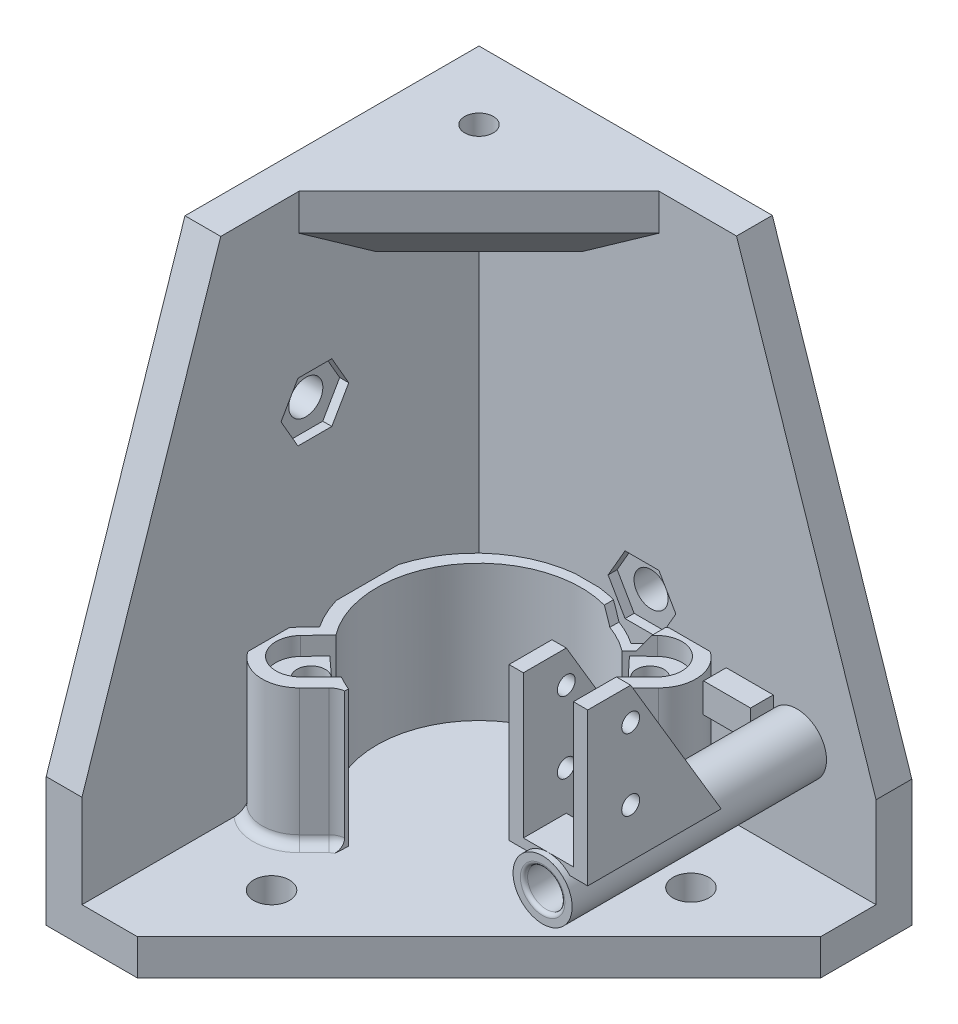
SolidWorks part; units mm, degrees
ref_plane "Front" through (0, 0, 0) normal (0, 0, 1) x (1, 0, 0)
ref_plane "Top" through (0, 0, 0) normal (0, 1, 0) x (1, 0, 0)
ref_plane "Right" through (0, 0, 0) normal (1, 0, 0) x (0, 0, -1)
sketch "Sketch1" plane through (0, 0, 0) normal (0, 1, 0) x (1, 0, 0)
  line L0 (0, 0) -> (0, 60.5)
  line L1 (0, -55) -> (0, 55) construction
  line L2 (0, 60.5) -> (60.5, 60.5)
  line L3 (60.5, 60.5) -> (60.5, 47.75)
  line L4 (60.5, 47.75) -> (12.75, 0)
  line L5 (-55, 0) -> (55, 0) construction
  line L6 (12.75, 0) -> (0, 0)
  dimension "D1" = 60.5
  dimension "D2" = 12.75
extrude "Boss-Extrude1" add sketch "Sketch1" along normal blind 5
sketch "Sketch4" plane through (0, 0, 0) normal (-1, 0, 0) x (0, 0, 1)
  line L0 (-60.5, 5) -> (-60.5, 76.1962)
  line L1 (-60.5, 76.1962) -> (-19.4, 76.1962)
  line L2 (-19.4, 76.1962) -> (0, 18.0048)
  line L3 (0, 18.0048) -> (0, 5)
  line L4 (0, -2.75) -> (0, 2.75) construction
  line L5 (-60.5, 5) -> (0, 5) construction
  line L6 (-60.5, 5) -> (0, 5)
  dimension "D1" = 71.1962
  dimension "D2" = 41.1
  dimension "D3" = 61.34
extrude "Boss-Extrude2" add sketch "Sketch4" against normal blind 5
sketch "Sketch5" plane through (0, 0, -60.5) normal (0, 0, -1) x (-1, 0, 0)
  line L0 (0, 76.1962) -> (-41, 76.1962)
  line L1 (-41, 76.1962) -> (-60.5, 17.7009)
  line L2 (-60.5, 17.7009) -> (-60.5, 5)
  line L6 (-60.5, 0) -> (0, 0)
  line L7 (0, 0) -> (0, 76.1962)
  line L8 (0, 76.1962) -> (-5, 76.1962)
  line L9 (-5, 76.1962) -> (-5, 5)
  line L10 (-5, 5) -> (-60.5, 5)
  line L11 (-60.5, 5) -> (-60.5, 0)
  line L12 (-60.5, 0) -> (0, 0)
  line L13 (0, 0) -> (0, 76.1962)
  line L14 (0, 76.1962) -> (-5, 76.1962)
  line L15 (-5, 76.1962) -> (-5, 5)
  line L16 (-5, 5) -> (-60.5, 5)
  line L17 (-60.5, 5) -> (-60.5, 0)
  line M13 (-5, 76.1962) -> (-5, 5)
  line M14 (-5, 5) -> (-60.5, 5)
  dimension "D2" = 41
  dimension "D3" = 61.66
  dimension "D1" = 0
extrude "Boss-Extrude3" add sketch "Sketch5" against normal blind 5 contours L1 L2 L0 M14 M13 region at (29.1655, 37.8824, -60.5)
sketch "Sketch6" plane through (0, 5, 0) normal (0, 1, 0) x (1, 0, 0)
  line L0 (60.5, 60.5) -> (0, 60.5) construction
  line L4 (0, 19.4) -> (0, 0)
  line L5 (60.5, 55.5) -> (5, 55.5)
  line L6 (5, 55.5) -> (5, 0)
  line L7 (5, 0) -> (12.75, 0)
  line L8 (12.75, 0) -> (60.5, 47.75)
  line L9 (60.5, 47.75) -> (60.5, 55.5)
  line L10 (60.5, 55.5) -> (5, 55.5)
  line L11 (5, 55.5) -> (5, 0)
  line L12 (5, 0) -> (12.75, 0)
  line L13 (12.75, 0) -> (60.5, 47.75)
  line L14 (60.5, 47.75) -> (60.5, 55.5)
  line L15 (0, 0) -> (5, 0)
  line L16 (5, 0) -> (5, 19.4)
  line L17 (5, 19.4) -> (0, 19.4)
  line L18 (0, 19.4) -> (0, 0)
  line L19 (0, 0) -> (5, 0)
  line L20 (5, 0) -> (5, 19.4)
  line L21 (5, 19.4) -> (0, 19.4)
  line L24 (0, 60.5) -> (0, 19.4)
  line L25 (0, 19.4) -> (5, 19.4)
  line L26 (5, 19.4) -> (5, 55.5)
  line L27 (5, 55.5) -> (41, 55.5)
  line L28 (41, 55.5) -> (41, 60.5)
  line L29 (41, 60.5) -> (0, 60.5)
  line L30 (0, 60.5) -> (0, 19.4)
  line L31 (0, 19.4) -> (5, 19.4)
  line L32 (5, 19.4) -> (5, 55.5)
  line L33 (5, 55.5) -> (41, 55.5)
  line L34 (41, 55.5) -> (41, 60.5)
  line L35 (41, 60.5) -> (0, 60.5)
  circle A0 centre (16.5, 15) radius 2.5
  circle A1 centre (45.5, 44.625) radius 2.5
  dimension "D1" = 5
  dimension "D2" = 5
  dimension "D3" = 0
  dimension "D4" = 15
  dimension "D6" = 16.5
  dimension "D7" = 15
  dimension "D9" = 15.875
  dimension "D5" = 0
  dimension "D8" = 0
extrude "Cut-Extrude1" cut sketch "Sketch6" against normal through all contours A0 | A1 region at (16.5, 5, -15) region at (45.5, 5, -44.625)
sketch "Sketch9" plane through (0, 0, -55.5) normal (0, 0, 1) x (1, 0, 0)
  line L1 (5, 76.1962) -> (5, 5) construction
  line L5 (0, 0) -> (60.5, 0)
  line L6 (0, 76.1962) -> (0, 0)
  line L7 (41, 76.1962) -> (0, 76.1962)
  line L8 (60.5, 17.7009) -> (41, 76.1962)
  line L9 (60.5, 0) -> (60.5, 17.7009)
  line L10 (0, 0) -> (60.5, 0)
  line L11 (0, 76.1962) -> (0, 0)
  line L12 (41, 76.1962) -> (0, 76.1962)
  line L13 (60.5, 17.7009) -> (41, 76.1962)
  line L14 (60.5, 0) -> (60.5, 17.7009)
  line L15 (49.45, 19.0462) -> (49.45, 3.6199) construction
  circle A0 centre (49.45, 19.0462) radius 4.1275
  circle A1 centre (49.45, 19.0462) radius 2.6035
  dimension "D2" = 5.207
  dimension "D3" = 1.524
  dimension "D4" = 57.15
  dimension "D5" = 44.45
  dimension "D1" = 0
extrude "Boss-Extrude5" add sketch "Sketch9" along normal blind 35.56 contours A1 A0 region at (45.4392, 19.0462, -55.5)
fillet "Fillet1" radius 0.508 1 edges at (52.0535, 19.0462, -19.94)
sketch "Sketch14" plane through (0, 5, 0) normal (0, 1, 0) x (1, 0, 0)
  line L0 (13.4627, 27.5396) -> (14.7681, 26.7924)
  line L1 (12.75, 0) -> (60.5, 47.75) construction
  line L2 (36.625, 23.875) -> (5, 55.5) construction
  line L3 (5, 55.5) -> (60.5, 55.5) construction
  line L4 (32.9604, 47.0373) -> (33.7076, 45.7319)
  line L5 (14.8281, 26.8523) -> (11.8274, 23.8516)
  line L6 (6.723, 28.8027) -> (9.1327, 31.3641)
  line L7 (33.6477, 45.6719) -> (36.6484, 48.6726)
  line L8 (31.6973, 53.777) -> (29.1359, 51.3673)
  line L9 (15.0744, 24.4582) -> (13.006, 22.3898)
  line L10 (5.6561, 29.7396) -> (7.0609, 31.1444)
  line L11 (36.0418, 45.4256) -> (38.1102, 47.494)
  line L12 (30.7604, 54.8439) -> (28.83, 52.9135)
  line L13 (18.1324, 24.8665) -> (30.5234, 17.7734)
  line L14 (35.6335, 42.3676) -> (42.7266, 29.9766)
  line L15 (31.7409, 18.9909) -> (18.852, 25.7543)
  line L16 (41.5091, 28.7591) -> (34.7457, 41.648)
  line L17 (16.5689, 25.6946) -> (16.5343, 25.1798)
  line L18 (34.7457, 41.648) -> (35.7996, 42.0774)
  circle A0 centre (20.5607, 39.9393) radius 14.2875
  arc A1 (11.8274, 23.8516) -> (6.723, 28.8027) centre (9.3129, 26.3661) cw
  arc A2 (36.6484, 48.6726) -> (31.6973, 53.777) centre (34.1339, 51.1871) ccw
  arc A3 (13.006, 22.3898) -> (5.6561, 29.7396) centre (9.3311, 26.0647) cw
  arc A4 (38.1102, 47.494) -> (30.7604, 54.8439) centre (34.4353, 51.1689) ccw
  arc A5 (7.0609, 31.1444) -> (28.83, 52.9135) centre (20.0709, 39.9035) cw
  arc A6 (36.0418, 45.4256) -> (35.6335, 42.3676) centre (37.8378, 43.6295) ccw
  arc A7 (15.0744, 24.4582) -> (18.1324, 24.8665) centre (16.8705, 22.6622) cw
  arc A9 (33.8602, 45.8844) -> (36.3595, 38.5726) centre (13.6025, 34.877) cw
  arc A10 (14.6156, 26.6398) -> (21.9274, 24.1405) centre (25.623, 46.8975) ccw
  point P40 (34.6689, 44.0527)
  point P43 (16.4473, 25.8311)
  line M13 (60.5, 55.5) -> (5, 55.5)
  line M14 (5, 55.5) -> (5, 0)
  line M16 (12.75, 0) -> (60.5, 47.75)
  dimension "D1" = 28.575
  dimension "D2" = 3.556
  dimension "D3" = 2.54
extrude "Boss-Extrude6" add sketch "Sketch14" along normal blind 19.05 contours L2 A0 L5 A1 L6 A5 L10 A3 L9 A7 L13 M16 M14 | L2 L14 A6 L11 A4 L12 A5 A0 L8 A2 L7 M16 M13 region at (7.691, 5, -30.3062) region at (10.0875, 5, -50.8829)
sketch "Sketch15" plane through (0, 76.1962, 0) normal (0, 1, 0) x (1, 0, 0)
  line L0 (5, 30.3375) -> (30.1625, 55.5)
  line L1 (0, -33.275) -> (0, 33.275) construction
  line L2 (41, 60.5) -> (0, 60.5) construction
  line L6 (0, 60.5) -> (0, 19.4)
  line L7 (0, 19.4) -> (5, 19.4)
  line L8 (5, 19.4) -> (5, 55.5)
  line L9 (5, 55.5) -> (41, 55.5)
  line L10 (41, 55.5) -> (41, 60.5)
  line L11 (41, 60.5) -> (0, 60.5)
  line L13 (0, 19.4) -> (5, 19.4)
  line L14 (5, 30.3375) -> (5, 55.5)
  line L15 (5, 55.5) -> (30.1625, 55.5)
  line L16 (41, 55.5) -> (41, 60.5)
  circle A0 centre (9.525, 50.975) radius 2
  line M11 (5, 19.4) -> (5, 55.5)
  line M12 (5, 55.5) -> (41, 55.5)
  dimension "D3" = 4
  dimension "D4" = 9.525
  dimension "D5" = 9.525
  dimension "D2" = 45
  dimension "D1" = 0
extrude "Boss-Extrude7" add sketch "Sketch15" against normal blind 12.7 contours L0 A0 M11 M12 region at (13.5472, 76.1962, -46.9528)
chamfer "Chamfer2" distance 7.62 angle 45 1 edges at (17.5813, 63.4962, -42.9187)
fillet "Fillet2" radius 1.27 7 edges at (39.6065, 5, -51.6871) (37.076, 5, -46.4598) (35.3202, 5, -43.9657) (8.8129, 5, -20.8935) (14.0402, 5, -23.424) (15.745, 5, -24.9392) (35.7165, 5, -42.2225)
sketch "Sketch16" plane through (0, 0, -55.5) normal (0, 0, 1) x (1, 0, 0)
  line L1 (46.1305, 23.2107) -> (38.2864, 23.2107)
  line L2 (46.1305, 23.2107) -> (46.1305, 19.0978)
  line L3 (46.1305, 19.0978) -> (38.2864, 19.0978)
  line L4 (38.2864, 23.2107) -> (38.2864, 19.0978)
extrude "Boss-Extrude8" add sketch "Sketch16" along normal blind 3.175
chamfer "Chamfer3" distance 1.27 angle 45 1 edges at (38.2864, 23.2107, -55.0794)
sketch "Sketch17" plane through (0, 5, 0) normal (0, 1, 0) x (1, 0, 0)
  line L0 (8.716, 30.9212) -> (14.047, 26.0712)
  line L1 (36.625, 23.875) -> (5, 55.5) construction
  line L2 (12.75, 0) -> (60.5, 47.75) construction
  line L3 (5, 55.5) -> (18.418, 55.5) construction
  line L4 (5, 55.5) -> (5, 44.2452) construction
  line L5 (29.6632, 51.8634) -> (34.5959, 46.6202)
  line L22 (37.3079, 55.5) -> (31.5627, 55.5)
  line L23 (30.7604, 54.8439) -> (28.83, 52.9135)
  line L24 (21.7238, 55.5) -> (18.418, 55.5)
  line L25 (5, 44.2452) -> (5, 35.5618)
  line L26 (7.0609, 31.1444) -> (5.6561, 29.7396)
  line L27 (5, 28.9373) -> (5, 23.1921)
  line L28 (13.006, 22.3898) -> (15.0744, 24.4582)
  line L29 (16.5343, 25.1798) -> (16.5689, 25.6946)
  line L30 (16.5343, 25.1798) -> (16.5689, 25.6946)
  line L31 (35.539, 41.9712) -> (35.7996, 42.0774)
  line L32 (35.539, 41.9712) -> (35.7996, 42.0774)
  line L33 (14.6156, 26.6398) -> (11.8274, 23.8516)
  line L34 (6.723, 28.8027) -> (9.1327, 31.3641)
  line L35 (29.1359, 51.3673) -> (31.6973, 53.777)
  line L36 (36.6484, 48.6726) -> (33.8602, 45.8844)
  line L40 (35.7996, 42.0774) -> (35.6335, 42.3676)
  line L41 (36.0418, 45.4256) -> (38.1102, 47.494)
  line L43 (37.3079, 55.5) -> (31.5627, 55.5)
  line L44 (30.7604, 54.8439) -> (28.83, 52.9135)
  line L45 (21.7238, 55.5) -> (18.418, 55.5)
  line L46 (5, 44.2452) -> (5, 35.5618)
  line L47 (7.0609, 31.1444) -> (5.6561, 29.7396)
  line L48 (5, 28.9373) -> (5, 23.1921)
  line L49 (13.006, 22.3898) -> (15.0744, 24.4582)
  line L54 (14.6156, 26.6398) -> (11.8274, 23.8516)
  line L55 (6.723, 28.8027) -> (9.1327, 31.3641)
  line L56 (29.1359, 51.3673) -> (31.6973, 53.777)
  line L57 (36.6484, 48.6726) -> (33.8602, 45.8844)
  line L61 (35.7996, 42.0774) -> (35.6335, 42.3676)
  line L62 (36.0418, 45.4256) -> (38.1102, 47.494)
  circle A1 centre (33.6908, 50.7324) radius 2.1828
  circle A2 centre (10.0204, 27.0078) radius 1.9844
  circle A3 centre (33.6908, 50.7324) radius 1.9288
  arc A15 (38.1102, 47.494) -> (37.3079, 55.5) centre (34.4353, 51.1689) ccw
  arc A17 (31.5627, 55.5) -> (30.7604, 54.8439) centre (34.4353, 51.1689) ccw
  arc A18 (28.83, 52.9135) -> (21.7238, 55.5) centre (20.0709, 39.9035) ccw
  arc A19 (18.418, 55.5) -> (5, 44.2452) centre (20.0709, 39.9035) ccw
  arc A20 (5, 35.5618) -> (7.0609, 31.1444) centre (20.0709, 39.9035) ccw
  arc A21 (5.6561, 29.7396) -> (5, 28.9373) centre (9.3311, 26.0647) ccw
  arc A22 (5, 23.1921) -> (13.006, 22.3898) centre (9.3311, 26.0647) ccw
  arc A23 (16.5343, 25.1798) -> (15.0744, 24.4582) centre (16.8705, 22.6622) ccw
  arc A24 (14.6156, 26.6398) -> (16.5689, 25.6946) centre (25.623, 46.8975) ccw
  arc A25 (6.723, 28.8027) -> (11.8274, 23.8516) centre (9.3129, 26.3661) ccw
  arc A26 (29.1359, 51.3673) -> (9.1327, 31.3641) centre (20.5607, 39.9393) ccw
  arc A27 (36.6484, 48.6726) -> (31.6973, 53.777) centre (34.1339, 51.1871) ccw
  arc A28 (35.539, 41.9712) -> (33.8602, 45.8844) centre (13.6025, 34.877) ccw
  arc A29 (36.0418, 45.4256) -> (35.6335, 42.3676) centre (37.8378, 43.6295) ccw
  arc A30 (38.1102, 47.494) -> (37.3079, 55.5) centre (34.4353, 51.1689) ccw
  arc A32 (31.5627, 55.5) -> (30.7604, 54.8439) centre (34.4353, 51.1689) ccw
  arc A33 (28.83, 52.9135) -> (21.7238, 55.5) centre (20.0709, 39.9035) ccw
  arc A34 (18.418, 55.5) -> (5, 44.2452) centre (20.0709, 39.9035) ccw
  arc A35 (5, 35.5618) -> (7.0609, 31.1444) centre (20.0709, 39.9035) ccw
  arc A36 (5.6561, 29.7396) -> (5, 28.9373) centre (9.3311, 26.0647) ccw
  arc A37 (5, 23.1921) -> (13.006, 22.3898) centre (9.3311, 26.0647) ccw
  arc A38 (16.5343, 25.1798) -> (15.0744, 24.4582) centre (16.8705, 22.6622) ccw
  arc A39 (14.6156, 26.6398) -> (16.5689, 25.6946) centre (25.623, 46.8975) ccw
  arc A40 (6.723, 28.8027) -> (11.8274, 23.8516) centre (9.3129, 26.3661) ccw
  arc A41 (29.1359, 51.3673) -> (9.1327, 31.3641) centre (20.5607, 39.9393) ccw
  arc A42 (36.6484, 48.6726) -> (31.6973, 53.777) centre (34.1339, 51.1871) ccw
  arc A43 (35.539, 41.9712) -> (33.8602, 45.8844) centre (13.6025, 34.877) ccw
  arc A44 (36.0418, 45.4256) -> (35.6335, 42.3676) centre (37.8378, 43.6295) ccw
  line M44 (33.8602, 45.8844) -> (36.6484, 48.6726)
  arc M45 (36.6484, 48.6726) -> (31.6973, 53.777) centre (34.1339, 51.1871) ccw
  line M46 (31.6973, 53.777) -> (29.1359, 51.3673)
  line M48 (9.1327, 31.3641) -> (6.723, 28.8027)
  arc M49 (6.723, 28.8027) -> (11.8274, 23.8516) centre (9.3129, 26.3661) ccw
  line M50 (11.8274, 23.8516) -> (14.6156, 26.6398)
  dimension "D2" = 3.9688
  dimension "D3" = 0.254
  dimension "D1" = 0
extrude "Boss-Extrude9" add sketch "Sketch17" along normal offset from surface (16.51 mm away) 2.54 contours L5 A1 M46 M44 M45 | L0 M48 M49 M50 | A1 L5 A3 region at (11.3737, 5, -28.4876) region at (30.7585, 5, -52.737) region at (33.0584, 5, -52.7569) up to face at (20.9693, 24.05, -39.9839)
sketch "Sketch18" plane through (0, 0, 0) normal (-1, 0, 0) x (0, 0, 1)
  line L0 (-60.5, 76.1962) -> (-60.5, 0) construction
  line L1 (33.275, 0) -> (-33.275, 0) construction
  circle A0 centre (-32.56, 49.53) radius 2.3813
  dimension "D1" = 27.94
  dimension "D2" = 49.53
  dimension "D3" = 4.7625
extrude "Cut-Extrude2" cut sketch "Sketch18" against normal up to next
sketch "Sketch19" plane through (0, 0, -60.5) normal (0, 0, -1) x (-1, 0, 0)
  line L0 (0, 33.275) -> (0, -33.275) construction
  line L1 (33.275, 0) -> (-33.275, 0) construction
  circle A0 centre (-27.7812, 26.1937) radius 2.3813
  dimension "D1" = 27.7812
  dimension "D2" = 26.1937
  dimension "D3" = 4.7625
extrude "Cut-Extrude3" cut sketch "Sketch19" against normal up to next
sketch "Sketch20" plane through (0, 0, -55.5) normal (0, 0, 1) x (1, 0, 0)
  line L1 (32.5155, 26.1938) -> (30.1484, 30.2938)
  line L2 (30.1484, 30.2938) -> (25.4141, 30.2938)
  line L3 (25.4141, 30.2938) -> (23.047, 26.1938)
  line L4 (23.047, 26.1938) -> (25.4141, 22.0938)
  line L5 (25.4141, 22.0938) -> (30.1484, 22.0938)
  line L6 (30.1484, 22.0938) -> (32.5155, 26.1938)
  circle A0 centre (27.7812, 26.1937) radius 2.3813 construction
  circle A1 centre (27.7812, 26.1937) radius 2.3813
  circle A2 centre (27.7812, 26.1937) radius 4.1 construction
  dimension "D1" = 8.2
extrude "Cut-Extrude4" cut sketch "Sketch20" against normal blind 1.27 and the other way up to vertex (4.1327 mm away) contours L1 L2 L3 L4 L5 L6 other way up to point (29.1359, 24.05, -51.3673)
sketch "Sketch21" plane through (5, 0, 0) normal (1, 0, 0) x (0, 0, -1)
  line L1 (34.9271, 53.63) -> (30.1929, 53.63)
  line L2 (30.1929, 53.63) -> (27.8257, 49.53)
  line L3 (27.8257, 49.53) -> (30.1929, 45.43)
  line L4 (30.1929, 45.43) -> (34.9271, 45.43)
  line L5 (34.9271, 45.43) -> (37.2943, 49.53)
  line L6 (37.2943, 49.53) -> (34.9271, 53.63)
  circle A0 centre (32.56, 49.53) radius 2.3813 construction
  circle A1 centre (32.56, 49.53) radius 2.3812
  circle A2 centre (32.56, 49.53) radius 4.1 construction
  dimension "D1" = 8.2
extrude "Cut-Extrude5" cut sketch "Sketch21" against normal blind 1.27 contours L1 L2 L3 L4 L5 L6
sketch "Sketch23" plane through (0, 0, 0) normal (0, 1, 0) x (1, 0, 0)
  line L1 (60.5, 60.5) -> (101.14, 60.5)
  line L2 (60.5, 60.5) -> (60.5, 24.94)
  line L3 (60.5, 24.94) -> (101.14, 24.94)
  line L4 (101.14, 60.5) -> (101.14, 24.94)
  dimension "D1" = 40.64
  dimension "D2" = 35.56
extrude "Boss-Extrude12" [suppressed] add sketch "Sketch23" along normal blind 5.08
sketch "Sketch24" [suppressed] plane through (0, 5.08, 0) normal (0, 1, 0) x (1, 0, 0)
  line L0 (101.14, 60.5) -> (60.5, 60.5) construction
  line L1 (60.5, 47.75) -> (60.5, 55.5) construction
  circle A0 centre (65.58, 55.42) radius 1.7145
  circle A1 centre (96.06, 55.42) radius 1.7145
  circle A2 centre (96.06, 29.258) radius 1.7145
  circle A3 centre (65.58, 29.258) radius 1.7145
  dimension "D1" = 3.429
  dimension "D2" = 26.162
  dimension "D3" = 30.48
  dimension "D4" = 5.08
  dimension "D5" = 5.08
extrude "Cut-Extrude6" [suppressed] cut sketch "Sketch24" against normal up to next
sketch "Sketch25" plane through (0, 63.4962, 0) normal (0, -1, 0) x (1, 0, 0)
  line L1 (13.5665, -50.975) -> (11.5457, -47.475)
  line L2 (11.5457, -47.475) -> (7.5043, -47.475)
  line L3 (7.5043, -47.475) -> (5.4835, -50.975)
  line L4 (5.4835, -50.975) -> (7.5043, -54.475)
  line L5 (7.5043, -54.475) -> (11.5457, -54.475)
  line L6 (11.5457, -54.475) -> (13.5665, -50.975)
  circle A0 centre (9.525, -50.975) radius 2 construction
  circle A1 centre (9.525, -50.975) radius 2
  circle A2 centre (9.525, -50.975) radius 3.5 construction
  dimension "D1" = 7
extrude "Cut-Extrude7" cut sketch "Sketch25" against normal blind 4
ref_plane "Plane1" through (0, 23.1737, 0) normal (0, 1, 0) x (1, 0, 0)
sketch "Sketch26" plane through (0, 23.1737, 0) normal (0, 1, 0) x (1, 0, 0)
  line L0 (45.3225, 19.94) -> (53.5775, 19.94) construction
  line L1 (43.95, 26.75) -> (54.95, 26.75)
  line L2 (43.95, 26.75) -> (43.95, 20.75)
  line L3 (43.95, 20.75) -> (54.95, 20.75)
  line L4 (54.95, 26.75) -> (54.95, 20.75)
  line L5 (43.95, 26.75) -> (54.95, 20.75) construction
  line L6 (43.95, 20.75) -> (54.95, 26.75) construction
  line L7 (45.3225, 19.94) -> (53.5775, 19.94)
  line L9 (45.95, 26.75) -> (52.95, 26.75)
  line L10 (45.95, 26.75) -> (45.95, 20.75)
  line L11 (45.95, 20.75) -> (52.95, 20.75)
  line L12 (52.95, 26.75) -> (52.95, 20.75)
  line L13 (45.95, 26.75) -> (52.95, 20.75) construction
  line L14 (45.95, 20.75) -> (52.95, 26.75) construction
  point P0 (49.45, 23.75)
  point P5 (0, 0)
  point P6 (0, 0)
  point P9 (49.45, 19.94)
  point P10 (49.45, 23.75)
  dimension "D1" = 11
  dimension "D2" = 6
  dimension "D3" = 3.81
  dimension "D4" = 2
extrude "Boss-Extrude13" add sketch "Sketch26" along normal blind 20 separate body contours L10 L1 L2 L3 | L1 L12 L3 L4 region at (44.95, 23.1737, -23.75) region at (53.95, 23.1737, -23.75)
extrude "Boss-Extrude14" add sketch "Sketch26<4>" against normal blind 1.3 contours L10 L1 L2 L3 | L12 L1 L10 L3 | L1 L12 L3 L4 region at (44.95, 23.1737, -23.75) region at (49.45, 23.1737, -23.75) region at (53.95, 23.1737, -23.75)
sketch "Sketch26<4>" plane through (0, 23.1737, 0) normal (0, 1, 0) x (1, 0, 0) same geometry as "Sketch26"
sketch "Sketch27" plane through (54.95, 0, 0) normal (1, 0, 0) x (0, 0, -1)
  line L0 (26.75, 43.1737) -> (39.4036, 21.8737)
  line L1 (26.75, 21.8737) -> (39.4036, 21.8737)
  line L2 (26.75, 43.1737) -> (26.75, 21.8737)
  point P2 (0, 0)
  point P5 (26.0983, 43.9203)
  point P6 (0, 0)
  point P7 (0, 0)
  point P9 (0, 0)
extrude "Boss-Extrude15" add sketch "Sketch27" against normal up to surface (2 mm away) from offset 0 up to face at (52.95, 33.1737, -23.75)
sketch "Sketch28" plane through (43.95, 0, 0) normal (-1, 0, 0) x (0, 0, 1)
  line L6 (-26.75, 23.1737) -> (-20.75, 23.1737)
  line L7 (-20.75, 23.1737) -> (-20.75, 43.1737)
  line L8 (-20.75, 43.1737) -> (-26.75, 43.1737)
  line L9 (-26.75, 43.1737) -> (-39.4036, 21.8737)
  line L10 (-39.4036, 21.8737) -> (-26.75, 21.8737)
  line L11 (-26.75, 21.8737) -> (-26.75, 23.1737)
  line L12 (-26.75, 23.1737) -> (-20.75, 23.1737)
  line L13 (-20.75, 23.1737) -> (-20.75, 43.1737)
  line L14 (-20.75, 43.1737) -> (-26.75, 43.1737)
  line L15 (-26.75, 43.1737) -> (-39.4036, 21.8737)
  line L16 (-39.4036, 21.8737) -> (-26.75, 21.8737)
  line L17 (-26.75, 21.8737) -> (-26.75, 23.1737)
  dimension "D1" = 0
extrude "Boss-Extrude16" add sketch "Sketch28" against normal up to surface (2 mm away) up to face at (45.95, 33.1737, -23.75)
sketch "Sketch30" plane through (52.95, 0, 0) normal (-1, 0, 0) x (0, 0, 1)
  line L6 (-26.75, 23.1737) -> (-20.75, 23.1737)
  line L7 (-20.75, 23.1737) -> (-20.75, 43.1737)
  line L8 (-20.75, 43.1737) -> (-26.75, 43.1737)
  line L9 (-26.75, 43.1737) -> (-39.4036, 21.8737)
  line L10 (-39.4036, 21.8737) -> (-26.75, 21.8737)
  line L11 (-26.75, 21.8737) -> (-26.75, 23.1737)
  line L12 (-26.75, 23.1737) -> (-20.75, 23.1737)
  line L13 (-20.75, 23.1737) -> (-20.75, 43.1737)
  line L14 (-20.75, 43.1737) -> (-26.75, 43.1737)
  line L15 (-26.75, 43.1737) -> (-39.4036, 21.8737)
  line L16 (-39.4036, 21.8737) -> (-26.75, 21.8737)
  line L17 (-26.75, 21.8737) -> (-26.75, 23.1737)
  circle A0 centre (-26.75, 28.6737) radius 1.25
  circle A1 centre (-26.75, 38.6737) radius 1.25
  dimension "D2" = 5.5
  dimension "D3" = 10
  dimension "D4" = 2.5
  dimension "D5" = 2.5
  dimension "D6" = 6
  dimension "D1" = 0
extrude "Cut-Extrude8" cut sketch "Sketch30" against normal through all and the other way up to surface (9 mm away) contours A1 | A0 region at (52.95, 28.6737, -26.75) region at (52.95, 38.6737, -26.75) other way up to face at (43.95, 32.5237, -26.9134)
